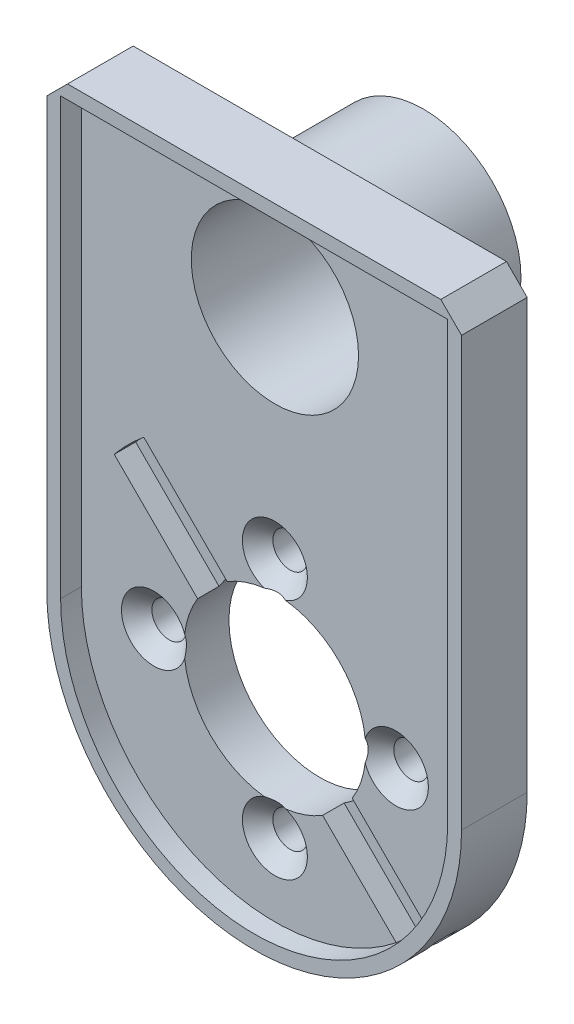
SolidWorks part; units mm, degrees
ref_plane "Front Plane" through (0, 0, 0) normal (0, 0, 1) x (1, 0, 0)
ref_plane "Top Plane" through (0, 0, 0) normal (0, 1, 0) x (1, 0, 0)
ref_plane "Right Plane" through (0, 0, 0) normal (1, 0, 0) x (0, 0, -1)
sketch "Sketch1" plane through (0, 0, 0) normal (0, 0, 1) x (1, 0, 0)
  circle A0 centre (0, 0) radius 30
  circle A1 centre (0, 0) radius 13.15
  circle A3 centre (-17.5, 0) radius 2.5
  circle A4 centre (0, 17.5) radius 2.5
  circle A5 centre (17.5, 0) radius 2.5
  circle A6 centre (0, -17.5) radius 2.5
  dimension "D1" = 60
  dimension "D2" = 26.3
extrude "Boss-Extrude1" add sketch "Sketch1" along normal blind 6.5
sketch "Sketch2" plane through (0, 0, 6.5) normal (0, 0, 1) x (1, 0, 0)
  line L2 (0, 0) -> (21.2132, -21.2132)
  circle A2 centre (0, 0) radius 30 construction
ref_plane "Plane1" through (21.2132, -21.2132, 6.5) normal (0.7071, -0.7071, 0) x (0, 0, -1)
sketch "Sketch3" plane through (21.2132, -21.2132, 6.5) normal (0.7071, -0.7071, 0) x (0, 0, -1)
  line L0 (3.1, 3.025) -> (3.1, -3.025)
  line L1 (0, 30) -> (0, -30) construction
  line L3 (3.1, 3.025) -> (0, 3.025)
  line L4 (0, 3.025) -> (0, -3.025)
  line L5 (0, -3.025) -> (3.1, -3.025)
  point P8 (4.8, 0)
  point P9 (3.1, 0)
  dimension "D1" = 0
extrude "Cut-Extrude1" cut sketch "Sketch3" against normal through all both and the other way through all
sketch "Sketch6" plane through (0, 0, 6.5) normal (0, 0, 1) x (1, 0, 0)
  line L0 (-28, 0) -> (-30, 0)
  line L1 (28, 0) -> (30, 0)
  arc A0 (-30, 0) -> (30, 0) centre (0, 0) ccw
  arc A1 (-28, 0) -> (28, 0) centre (0, 0) ccw
  dimension "D1" = 2
extrude "Boss-Extrude4" add sketch "Sketch6" along normal blind 3
hole_wizard "CSK for M4 Oval Head Machine Screw1" positions "3DSketch1" profile "Sketch7" countersink size "M4" standard "ANSI Metric" end condition up to next
sketch3d "3DSketch1"
  line L0 (0, 17.5, 6.5) -> (0, 17.5, 0) construction
  line L1 (17.5, 0, 6.5) -> (17.5, 0, 0) construction
  line L2 (0, -17.5, 6.5) -> (0, -17.5, 0) construction
  line L3 (-17.5, 0, 6.5) -> (-17.5, 0, 0) construction
  point P0 (0, 17.5, 6.5)
  point P4 (17.5, 0, 6.5)
  point P8 (0, -17.5, 6.5)
  point P12 (-17.5, 0, 6.5)
sketch "Sketch7" plane through (0, 17.5, 6.5) normal (1, 0, 0) x (0, -1, 0)
  line L0 (0, 0) -> (0, 6.5)
  line L1 (0, 6.5) -> (2.25, 6.5)
  line L2 (2.25, 6.5) -> (2.25, 2.45)
  line L3 (2.25, 2.45) -> (4.7, 0)
  line L5 (4.7, 0) -> (0, 0)
  line L6 (-2.25, 2.45) -> (-4.7, 0) construction
  line L11 (0, -6.35) -> (0, 107.95) construction
  dimension "Thru Hole Dia." = 4.5
  dimension "Thru Hole Depth" = 6.5
  dimension "Near C'Sink Dia." = 9.4
  dimension "Near C'Sink Angle" = 90
sketch "Sketch8" plane through (0, 0, 0) normal (0, 0, -1) x (-1, 0, 0)
  line L0 (30, 0) -> (30, 65)
  line L1 (30, 65) -> (-30, 65)
  line L2 (-30, 65) -> (-30, 0)
  circle A0 centre (0, 0) radius 30 construction
  arc A1 (30, 0) -> (-30, 0) centre (0, 0) ccw
extrude "Boss-Extrude6" add sketch "Sketch8" against normal up to surface (6.5 mm away) up to face at (11.1431, 6.2379, 6.5)
sketch "Sketch10" plane through (0, 0, 6.5) normal (0, 0, 1) x (1, 0, 0)
  line L0 (-28, 0) -> (-30, 0)
  line L1 (-30, 0) -> (-30, 65)
  line L2 (-30, 65) -> (30, 65)
  line L3 (30, 65) -> (30, 0)
  line L4 (30, 0) -> (28, 0)
  line L5 (28, 0) -> (28, 63)
  line L6 (28, 63) -> (-28, 63)
  line L7 (-28, 63) -> (-28, 0)
  dimension "D1" = 2
extrude "Boss-Extrude8" add sketch "Sketch10" along normal up to surface (3 mm away) up to face at (0, -14.5, 9.5)
sketch "Sketch11" plane through (0, 0, 6.5) normal (0, 0, 1) x (1, 0, 0)
  circle A2 centre (0, 49) radius 12.1
extrude "Cut-Extrude2" cut sketch "Sketch11" against normal through all
sketch "Sketch12" plane through (0, 0, 0) normal (0, 0, -1) x (-1, 0, 0)
  circle A1 centre (0, 49) radius 12.1
extrude "Extrude-Thin2" add sketch "Sketch12" along normal blind 15 thin thin type one direction wall 2
chamfer "Chamfer1" distance 3 angle 45 2 edges at (30, 65, 4.75) (-30, 65, 4.75)
